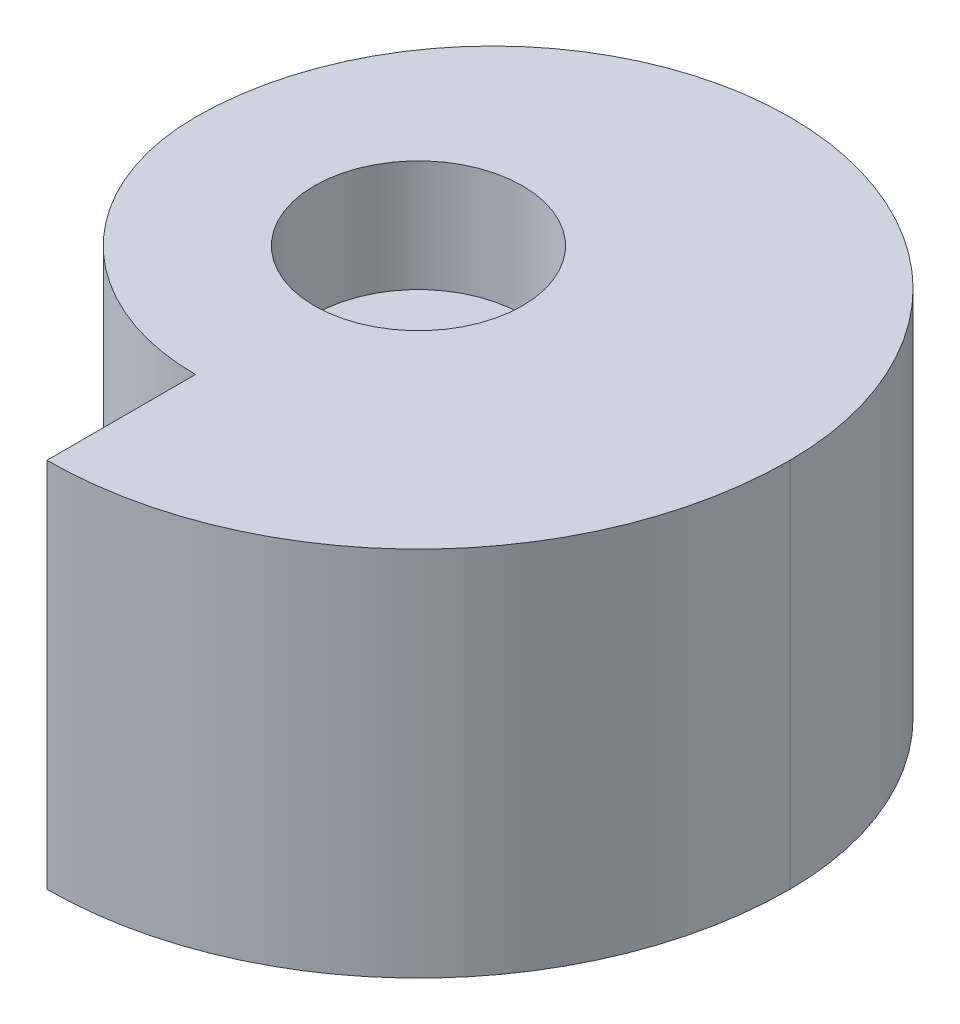
SolidWorks part; units mm, degrees
ref_plane "Front Plane" through (0, 0, 0) normal (0, 0, 1) x (1, 0, 0)
ref_plane "Top Plane" through (0, 0, 0) normal (0, 1, 0) x (1, 0, 0)
ref_plane "Right Plane" through (0, 0, 0) normal (1, 0, 0) x (0, 0, -1)
sketch "Sketch1" plane through (0, 0, 0) normal (0, 1, 0) x (1, 0, 0)
  circle A0 centre (0, 0) radius 6
  dimension "D1" = 12
extrude "Boss-Extrude1" add sketch "Sketch1" along normal blind 10
sketch "Sketch2" plane through (0, 10, 0) normal (0, 1, 0) x (1, 0, 0)
  circle A0 centre (0, 0) radius 2.8
  dimension "D1" = 5.6
extrude "Cut-Extrude1" cut sketch "Sketch2" against normal blind 3
sketch "Sketch3" plane through (0, 0, 0) normal (0, -1, 0) x (1, 0, 0)
  circle A0 centre (0, 0) radius 3.75
  dimension "D1" = 7.5
extrude "Cut-Extrude2" cut sketch "Sketch3" against normal blind 3
sketch "Sketch5" plane through (0, 0, 0) normal (0, -1, 0) x (1, 0, 0)
  line L2 (0, 6) -> (0, 10)
  circle A1 centre (0, 0) radius 6 construction
  arc A2 (-6, 0) -> (10, 0) centre (2, 0) ccw
  arc A4 (10, 0) -> (0, 10) centre (0, 0) ccw
  arc A5 (-6, 0) -> (0, 6) centre (0, 0) ccw
extrude "Boss-Extrude2" add sketch "Sketch5" against normal up to surface (10 mm away) up to face at (0, 10, 2.8)
